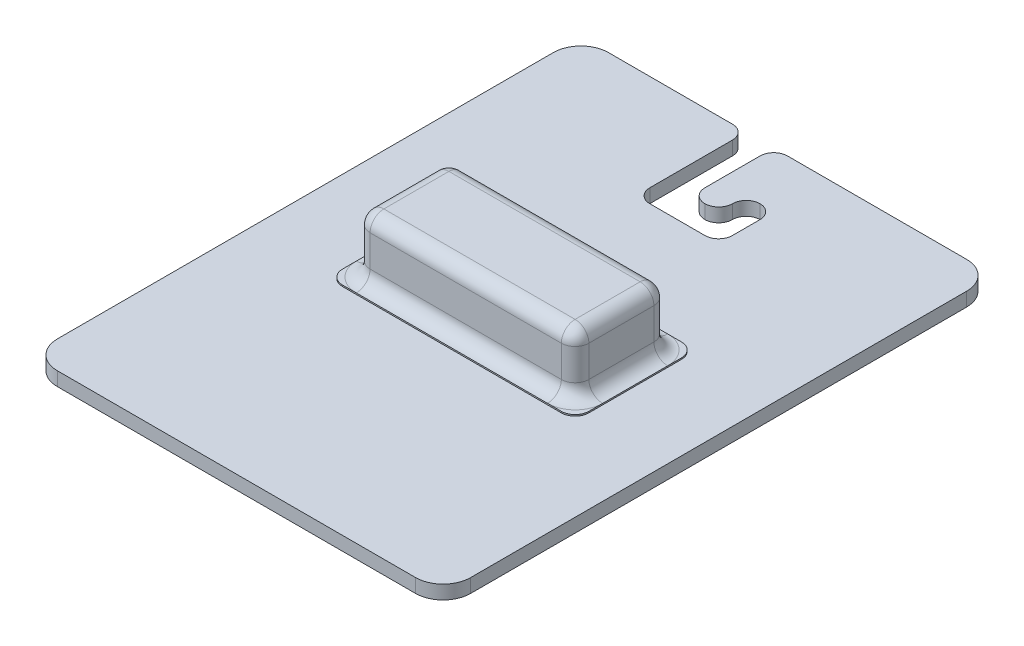
SolidWorks part; units mm, degrees
ref_plane "Front Plane" through (0, 0, 0) normal (0, 0, 1) x (1, 0, 0)
ref_plane "Top Plane" through (0, 0, 0) normal (0, 1, 0) x (1, 0, 0)
ref_plane "Right Plane" through (0, 0, 0) normal (1, 0, 0) x (0, 0, -1)
sketch "Sketch1" plane through (0, 0, 0) normal (0, 1, 0) x (1, 0, 0)
  line L1 (0, 0) -> (7.94, 0)
  line L2 (0, 0) -> (0, 3.36)
  line L3 (0, 3.36) -> (7.94, 3.36)
  line L4 (7.94, 0) -> (7.94, 3.36)
  dimension "D1" = 3.36
  dimension "D2" = 7.94
extrude "Boss-Extrude2" add sketch "Sketch1" along normal blind 2.14
fillet "Fillet1" radius 0.5 4 edges at (3.97, 2.14, -3.36) (7.94, 2.14, -1.68) (3.97, 2.14, 0) (0, 2.14, -1.68)
fillet "Fillet2" radius 0.5 8 edges at (0.1464, 1.9936, -3.2136) (7.7936, 1.9936, -3.2136) (0.1464, 1.9936, -0.1464) (7.94, 0.82, 0) (0, 0.82, -3.36) (7.94, 0.82, -3.36) (0, 0.82, 0) (7.7936, 1.9936, -0.1464)
sketch "Sketch2" plane through (0, 0, 0) normal (0, -1, 0) x (1, 0, 0)
  line L0 (7.94, -0.5) -> (7.94, -2.86) construction
  line L1 (-0.5, 0.5) -> (8.44, 0.5)
  line L2 (-0.5, 0.5) -> (-0.5, -3.86)
  line L3 (-0.5, -3.86) -> (8.44, -3.86)
  line L4 (8.44, 0.5) -> (8.44, -3.86)
  line L5 (-0.5, 0.5) -> (8.44, -3.86) construction
  line L6 (-0.5, -3.86) -> (8.44, 0.5) construction
  line L7 (7.44, -3.36) -> (0.5, -3.36) construction
  line L9 (0.5, 0) -> (7.44, 0) construction
  line L10 (0, -2.86) -> (0, -0.5) construction
  point P0 (3.97, -1.68)
  dimension "D1" = 0.5
  dimension "D2" = 0.5
  dimension "D3" = 0.5
  dimension "D4" = 0.5
extrude "Boss-Extrude3" add sketch "Sketch2" along normal blind 0.05
fillet "Fillet4" radius 0.5 12 edges at (0.1464, 0, -0.1464) (0, 0, -1.68) (0.1464, 0, -3.2136) (3.97, 0, -3.36) (7.7936, 0, -3.2136) (7.94, 0, -1.68) (7.7936, 0, -0.1464) (3.97, 0, 0) (-0.5, -0.025, 0.5) (-0.5, -0.025, -3.86) (8.44, -0.025, -3.86) (8.44, -0.025, 0.5)
shell "Shell1" thickness 0.05 removed face at (3.97, -0.05, -1.68)
sketch "Sketch3" plane through (0, -0.05, 0) normal (0, -1, 0) x (1, 0, 0)
  line L1 (-3.53, 8.32) -> (11.47, 8.32)
  line L2 (-3.53, 8.32) -> (-3.53, -11.68)
  line L3 (-3.53, -11.68) -> (11.47, -11.68)
  line L4 (11.47, 8.32) -> (11.47, -11.68)
  line L5 (-3.53, 8.32) -> (11.47, -11.68) construction
  line L6 (-3.53, -11.68) -> (11.47, 8.32) construction
  line L8 (-0.45, -0.1878) -> (-0.45, -3.1722) construction
  line L9 (7.94, 0.5) -> (0, 0.5) construction
  point P0 (3.97, -1.68)
  point P6 (3.97, 8.32)
  point P10 (3.97, 0.5)
  point P15 (-0.45, -1.68)
  dimension "D1" = 20
  dimension "D2" = 15
extrude "Boss-Extrude4" add sketch "Sketch3" along normal blind 0.5
fillet "Fillet5" radius 1 4 edges at (-3.53, -0.3, 8.32) (-3.53, -0.3, -11.68) (11.47, -0.3, -11.68) (11.47, -0.3, 8.32)
sketch "Sketch4" plane through (0, -0.05, 0) normal (0, 1, 0) x (1, 0, 0)
  line L0 (2.47, 11.68) -> (2.47, 7.68)
  line L1 (-2.53, 11.68) -> (10.47, 11.68) construction
  line L2 (2.47, 7.68) -> (5.47, 7.68)
  line L3 (5.47, 7.68) -> (5.47, 9.68)
  line L4 (5.47, 9.68) -> (4.47, 9.68)
  line L5 (4.47, 9.68) -> (4.47, 8.68)
  line L6 (4.47, 8.68) -> (3.47, 8.68)
  line L7 (3.47, 8.68) -> (3.47, 11.68)
  point P5 (3.97, 7.68)
  point P11 (3.97, 11.68)
  dimension "D1" = 1
  dimension "D2" = 1
  dimension "D3" = 2
  dimension "D4" = 1
  dimension "D5" = 3
  dimension "D6" = 4
extrude "Cut-Extrude1" cut sketch "Sketch4" against normal through all and the other way through all
fillet "Fillet6" radius 0.5 6 edges at (3.47, -0.3, -8.68) (4.47, -0.3, -8.68) (4.47, -0.3, -9.68) (5.47, -0.3, -9.68) (5.47, -0.3, -7.68) (2.47, -0.3, -7.68)
fillet "Fillet7" radius 0.5 2 edges at (3.47, -0.3, -11.68) (2.47, -0.3, -11.68)
